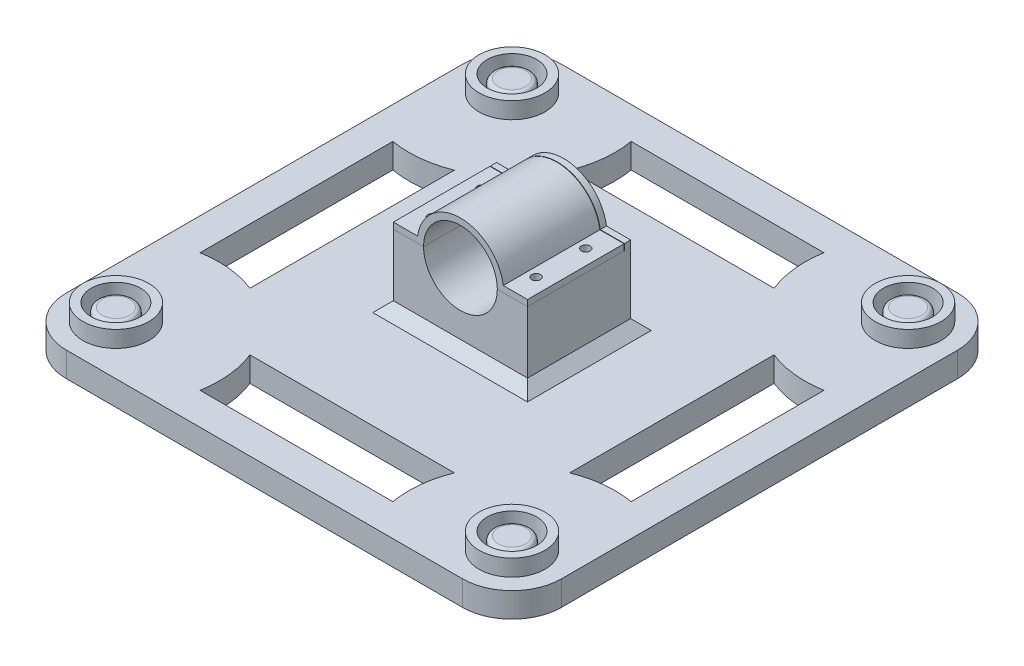
SolidWorks part; units mm, degrees
ref_plane "Front Plane" through (0, 0, 0) normal (0, 0, 1) x (1, 0, 0)
ref_plane "Top Plane" through (0, 0, 0) normal (0, 1, 0) x (1, 0, 0)
ref_plane "Right Plane" through (0, 0, 0) normal (1, 0, 0) x (0, 0, -1)
sketch "Sketch1" plane through (0, 0, 0) normal (0, 1, 0) x (1, 0, 0)
  line L1 (24, 0) -> (216, 0)
  line L2 (0, 24) -> (0, 216)
  line L3 (24, 240) -> (216, 240)
  line L4 (240, 24) -> (240, 216)
  arc A0 (24, 0) -> (0, 24) centre (24, 24) cw
  arc A1 (216, 0) -> (240, 24) centre (216, 24) ccw
  arc A2 (216, 240) -> (240, 216) centre (216, 216) cw
  arc A3 (0, 216) -> (24, 240) centre (24, 216) cw
  circle A4 centre (24, 216) radius 12
  circle A5 centre (216, 216) radius 12
  circle A7 centre (216, 24) radius 12
  circle A8 centre (24, 216) radius 8.7
  circle A9 centre (216, 216) radius 8.7
  circle A10 centre (216, 24) radius 8.7
  circle A11 centre (24, 24) radius 12
  circle A12 centre (24, 24) radius 8.7
  point P7 (0, 0)
  point P10 (240, 0)
  point P13 (240, 240)
  point P16 (0, 240)
  dimension "D3" = 24
  dimension "D4" = 24
  dimension "D5" = 24
  dimension "D6" = 24
  dimension "D7" = 24
  dimension "D8" = 17.4
  dimension "D9" = 17.4
  dimension "D10" = 17.4
  dimension "D11" = 17.4
  dimension "D1" = 240
  dimension "D2" = 240
extrude "Boss-Extrude1" add sketch "Sketch1" along normal blind 12 contours A3 L2 A0 L1 A1 L4 A2 L3 A11 A7 A5 A4 region at (120, 0, -120)
extrude "Boss-Extrude2" add sketch "Sketch1<3>" along normal blind 6 contours A11 A12 | A4 A8 | A5 A9 | A7 A10 region at (12.3394, 0, -216) region at (204.3394, 0, -216) region at (204.3394, 0, -24) region at (12.3394, 0, -24)
sketch "Sketch1<3>" plane through (0, 0, 0) normal (0, 1, 0) x (1, 0, 0) same geometry as "Sketch1"
extrude "Boss-Extrude3" add sketch "Sketch1<4>" along normal blind 18 contours A9 | A10 | A12 | A8 region at (24, 0, -216) region at (216, 0, -216) region at (216, 0, -24) region at (24, 0, -24)
sketch "Sketch1<4>" plane through (0, 0, 0) normal (0, 1, 0) x (1, 0, 0) same geometry as "Sketch1"
fillet "Fillet1" radius 2 4 edges at (216, 18, -207.3) (24, 18, -207.3) (216, 18, -15.3) (24, 18, -15.3)
sketch "Sketch2" plane through (0, 12, 0) normal (0, 1, 0) x (1, 0, 0)
  circle A0 centre (24, 24) radius 12
  circle A1 centre (24, 24) radius 16
  circle A2 centre (216, 24) radius 12
  circle A3 centre (216, 24) radius 16
  circle A4 centre (216, 216) radius 12
  circle A5 centre (216, 216) radius 16
  circle A6 centre (24, 216) radius 12
  circle A7 centre (24, 216) radius 16
  dimension "D1" = 32
  dimension "D2" = 32
  dimension "D3" = 32
  dimension "D4" = 32
extrude "Boss-Extrude4" add sketch "Sketch2" along normal blind 8
sketch "Sketch3" plane through (0, 12, 0) normal (0, 1, 0) x (1, 0, 0)
  line L0 (120, 240) -> (120, 0) construction
  line L1 (24, 240) -> (216, 240) construction
  line L2 (24, 0) -> (216, 0) construction
  line L3 (152.5, 90) -> (152.5, 110) construction
  line L4 (87.5, 150) -> (152.5, 150) construction
  line L5 (87.5, 150) -> (87.5, 90) construction
  line L6 (87.5, 90) -> (152.5, 90) construction
  line L7 (152.5, 150) -> (152.5, 90) construction
  line L8 (87.5, 150) -> (152.5, 90) construction
  line L9 (87.5, 90) -> (152.5, 150) construction
  line L10 (152.5, 150) -> (152.5, 130) construction
  line L12 (152.5, 130) -> (87.5, 130)
  line L13 (152.5, 130) -> (152.5, 145)
  line L14 (152.5, 145) -> (87.5, 145)
  line L15 (87.5, 130) -> (87.5, 145)
  line L16 (152.5, 110) -> (87.5, 110)
  line L17 (152.5, 110) -> (152.5, 95)
  line L18 (152.5, 95) -> (87.5, 95)
  line L19 (87.5, 110) -> (87.5, 95)
  point P6 (120, 120)
  dimension "D1" = 60
  dimension "D2" = 65
  dimension "D3" = 20
  dimension "D4" = 20
  dimension "D5" = 15
  dimension "D6" = 15
extrude "Boss-Extrude5" add sketch "Sketch3" along normal blind 35
sketch "Sketch10" plane through (0, 12, 0) normal (0, 1, 0) x (1, 0, 0)
  line L1 (87.5, 130) -> (152.5, 130)
  line L2 (87.5, 130) -> (87.5, 110)
  line L3 (87.5, 110) -> (152.5, 110)
  line L4 (152.5, 130) -> (152.5, 110)
extrude "Boss-Extrude6" add sketch "Sketch10" along normal blind 35
sketch "Sketch4" plane through (0, 0, -95) normal (0, 0, 1) x (1, 0, 0)
  line L0 (87.5, 47) -> (152.5, 47) construction
  circle A0 centre (120, 47) radius 17.875
  dimension "D1" = 35.75
extrude "Cut-Extrude1" cut sketch "Sketch4" against normal blind 49
chamfer "Chamfer1" distance 5 angle 45 4 edges at (152.5, 12, -120) (120, 12, -145) (87.5, 12, -120) (120, 12, -95)
sketch "Sketch11" plane through (0, 0, -145) normal (0, 0, -1) x (-1, 0, 0)
  circle A0 centre (-120, 47) radius 17.875
extrude "Boss-Extrude7" add sketch "Sketch11" against normal blind 3
sketch "Sketch9" plane through (0, 47, 0) normal (0, 1, 0) x (1, 0, 0)
  line L0 (145.1875, 104.3141) -> (145.1875, 95) construction
  line L2 (94.8125, 104.3141) -> (94.8125, 95) construction
  line L4 (137.875, 95) -> (152.5, 95) construction
  line L6 (87.5, 95) -> (102.125, 95) construction
  line L8 (145.1875, 130.5359) -> (145.1875, 106.4641) construction
  line L9 (94.8125, 130.5359) -> (94.8125, 106.4641) construction
  line L10 (102.125, 142) -> (87.5, 142) construction
  line L11 (87.5, 145) -> (87.5, 95) construction
  line L12 (94.8125, 132.6859) -> (94.8125, 142) construction
  line L13 (137.875, 142) -> (152.5, 142) construction
  line L15 (152.5, 95) -> (152.5, 145) construction
  line L16 (145.1875, 132.6859) -> (145.1875, 142) construction
  circle A0 centre (145.1875, 106.4641) radius 2.15
  circle A1 centre (94.8125, 106.4641) radius 2.15
  circle A2 centre (145.1875, 130.5359) radius 2.15
  circle A3 centre (94.8125, 130.5359) radius 2.15
  point P29 (94.8125, 106.4641)
  dimension "D2" = 4.3
  dimension "D4" = 4.3
  dimension "D5" = 4.3
  dimension "D6" = 4.3
extrude "Cut-Extrude2" cut sketch "Sketch9" against normal blind 8
sketch "Sketch13" plane through (0, 0, -142) normal (0, 0, 1) x (1, 0, 0)
  circle A0 centre (120, 47) radius 6.6
  dimension "D1" = 13.2
extrude "Cut-Extrude3" cut sketch "Sketch13" against normal blind 8
sketch "Sketch14" plane through (0, 0, -142) normal (0, 0, 1) x (1, 0, 0)
  line L0 (126.6, 47) -> (132.5, 47) construction
  line L1 (113.4, 47) -> (107.5, 47) construction
  line L2 (105.9, 47) -> (134.1, 47) construction
  circle A0 centre (120, 47) radius 6.6 construction
  circle A1 centre (132.5, 47) radius 1.6
  circle A2 centre (107.5, 47) radius 1.6
  dimension "D1" = 3.2
  dimension "D2" = 25
extrude "Cut-Extrude4" cut sketch "Sketch14" against normal blind 8
sketch "Sketch15" plane through (0, 0, -95) normal (0, 0, 1) x (1, 0, 0)
  line L0 (87.5, 47) -> (102.125, 47)
  line L1 (152.5, 47) -> (152.5, 50)
  line L2 (152.5, 50) -> (140.7846, 50)
  line L3 (87.5, 47) -> (87.5, 50)
  line L4 (87.5, 50) -> (99.2154, 50)
  line L5 (137.875, 47) -> (152.5, 47)
  arc A0 (137.875, 47) -> (102.125, 47) centre (120, 47) ccw
  arc A1 (140.7846, 50) -> (99.2154, 50) centre (120, 47) ccw
  dimension "D1" = 35.75
  dimension "D2" = 42
  dimension "D3" = 3
extrude "Boss-Extrude8" add sketch "Sketch15" against normal offset from surface (46.8 mm away) 0.2 separate body up to face at (134.1, 47, -142)
sketch "Sketch16" plane through (0, 50, 0) normal (0, 1, 0) x (1, 0, 0)
  circle A1 centre (145.1875, 130.5359) radius 2.15
  circle A2 centre (145.1875, 130.5359) radius 2.15
  circle A3 centre (94.8125, 106.4641) radius 2.15
  circle A4 centre (94.8125, 106.4641) radius 2.15
  circle A5 centre (145.1875, 106.4641) radius 2.15
  circle A6 centre (145.1875, 106.4641) radius 2.15
  circle A7 centre (94.8125, 130.5359) radius 2.15
  circle A8 centre (94.8125, 130.5359) radius 2.15
  dimension "D1" = 0
  dimension "D2" = 0
  dimension "D3" = 0
  dimension "D4" = 0
extrude "Cut-Extrude5" cut sketch "Sketch16" against normal blind 5.2
sketch "Sketch17" plane through (0, 0, -145) normal (0, 0, -1) x (-1, 0, 0)
  line L6 (-87.5, 47) -> (-87.5, 50)
  line L7 (-87.5, 50) -> (-99.2154, 50)
  line L8 (-140.7846, 50) -> (-152.5, 50)
  line L9 (-152.5, 50) -> (-152.5, 47)
  line L10 (-152.5, 47) -> (-137.875, 47)
  line L11 (-102.125, 47) -> (-87.5, 47)
  line L12 (-87.5, 47) -> (-87.5, 50)
  line L13 (-87.5, 50) -> (-99.2154, 50)
  line L14 (-140.7846, 50) -> (-152.5, 50)
  line L15 (-152.5, 50) -> (-152.5, 47)
  line L16 (-152.5, 47) -> (-137.875, 47)
  line L17 (-102.125, 47) -> (-87.5, 47)
  arc A2 (-99.2154, 50) -> (-140.7846, 50) centre (-120, 47) ccw
  arc A3 (-102.125, 47) -> (-137.875, 47) centre (-120, 47) ccw
  arc A4 (-99.2154, 50) -> (-140.7846, 50) centre (-120, 47) ccw
  arc A5 (-102.125, 47) -> (-137.875, 47) centre (-120, 47) ccw
  dimension "D1" = 0
extrude "Boss-Extrude9" add sketch "Sketch17" against normal up to surface (3 mm away) up to face at (134.1, 47, -142)
sketch "Sketch19" plane through (0, 12, 0) normal (0, 1, 0) x (1, 0, 0)
  line L2 (70.4516, 197.5) -> (169.5484, 197.5)
  line L3 (42.5, 169.5484) -> (42.5, 70.4516)
  line L4 (70.4516, 42.5) -> (169.5484, 42.5)
  line L5 (197.5, 169.5484) -> (197.5, 70.4516)
  line L8 (166.7253, 224.4853) -> (73.2747, 224.4853)
  line L9 (224.4853, 166.7253) -> (224.4853, 73.2747)
  line L10 (166.7253, 15.5147) -> (73.2747, 15.5147)
  line L11 (15.5147, 166.7253) -> (15.5147, 73.2747)
  arc A0 (73.2747, 15.5147) -> (70.4516, 42.5) centre (24, 24) ccw
  arc A1 (224.4853, 73.2747) -> (197.5, 70.4516) centre (216, 24) ccw
  arc A2 (166.7253, 224.4853) -> (169.5484, 197.5) centre (216, 216) ccw
  arc A3 (15.5147, 166.7253) -> (42.5, 169.5484) centre (24, 216) ccw
  arc A4 (197.5, 169.5484) -> (224.4853, 166.7253) centre (216, 216) ccw
  arc A5 (70.4516, 197.5) -> (73.2747, 224.4853) centre (24, 216) ccw
  arc A6 (42.5, 70.4516) -> (15.5147, 73.2747) centre (24, 24) ccw
  arc A7 (169.5484, 42.5) -> (166.7253, 15.5147) centre (216, 24) ccw
  point P4 (120, 120)
  point P17 (120, 120)
  dimension "D1" = 100
extrude "Cut-Extrude6" cut sketch "Sketch19" against normal blind 26.2
